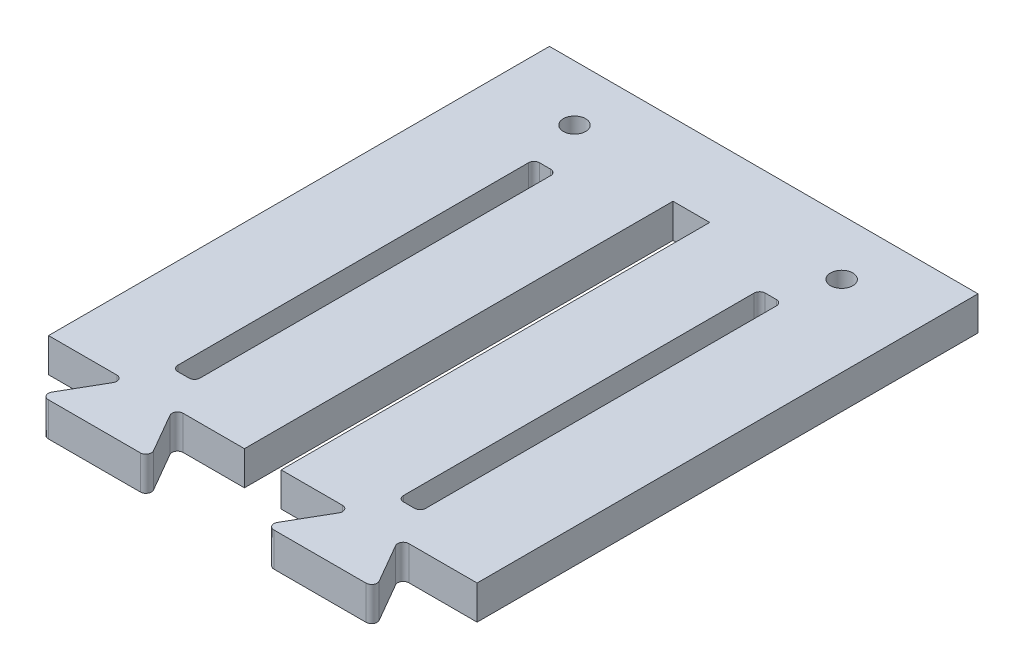
SolidWorks part; units mm, degrees
ref_plane "Front Plane" through (0, 0, 0) normal (0, 0, 1) x (1, 0, 0)
ref_plane "Top Plane" through (0, 0, 0) normal (0, 1, 0) x (1, 0, 0)
ref_plane "Right Plane" through (0, 0, 0) normal (1, 0, 0) x (0, 0, -1)
sketch "Sketch1" plane through (0, 0, 0) normal (0, 1, 0) x (1, 0, 0)
  line L0 (-19.25, 0) -> (-19.25, 45)
  line L1 (-19.25, 45) -> (19.25, 45)
  line L2 (19.25, 45) -> (19.25, 0)
  line L3 (19.25, 0) -> (12.25, 0)
  line L4 (12.25, 0) -> (15.1368, -5)
  line L5 (15.1368, -5) -> (5.1368, -5)
  line L6 (5.1368, -5) -> (8.0235, 0)
  line L7 (8.0235, 0) -> (-8.0235, 0)
  line L8 (-8.0235, 0) -> (-5.1368, -5)
  line L9 (-5.1368, -5) -> (-15.1368, -5)
  line L10 (-15.1368, -5) -> (-12.25, 0)
  line L11 (-12.25, 0) -> (-19.25, 0)
  point P13 (0, 0)
  dimension "D1" = 45
  dimension "D2" = 38.5
  dimension "D3" = 10
  dimension "D4" = 10
  dimension "D5" = 60
  dimension "D6" = 60
  dimension "D7" = 7
  dimension "D8" = 7
  dimension "D9" = 5
  dimension "D10" = 5
extrude "Boss-Extrude1" add sketch "Sketch1" along normal blind 3.05
fillet "Fillet1" radius 0.5 8 edges at (12.25, 1.525, 0) (15.1368, 1.525, 5) (5.1368, 1.525, 5) (8.0235, 1.525, 0) (-8.0235, 1.525, 0) (-5.1368, 1.525, 5) (-15.1368, 1.525, 5) (-12.25, 1.525, 0)
sketch "Sketch3" plane through (0, 3.05, 0) normal (0, 1, 0) x (1, 0, 0)
  line L0 (0, 40) -> (0, 0) construction
  line L2 (19.25, 45) -> (-19.25, 45) construction
  line L3 (-1.65, 38.5) -> (1.65, 38.5)
  line L4 (-1.65, 38.5) -> (-1.65, -1.5)
  line L5 (-1.65, -1.5) -> (1.65, -1.5)
  line L6 (1.65, 38.5) -> (1.65, -1.5)
  line L8 (-1.65, -2.7) -> (1.65, -2.7)
  line L9 (-1.65, -2.7) -> (-1.65, -3.7)
  line L10 (-1.65, -3.7) -> (1.65, -3.7)
  line L11 (1.65, -2.7) -> (1.65, -3.7)
  point P8 (0, 38.5)
  point P15 (0, -2.7)
  dimension "D1" = 3.3
  dimension "D2" = 40
  dimension "D3" = 6.5
  dimension "D4" = 1.2
  dimension "D5" = 1
extrude "Cut-Extrude2" cut sketch "Sketch3" against normal through all
sketch "Sketch8" plane through (0, 3.05, 0) normal (0, 1, 0) x (1, 0, 0)
  line L0 (0, 0) -> (0, 40) construction
  line L1 (-11.1368, 35.5) -> (-9.1368, 35.5)
  line L2 (-11.1368, 35.5) -> (-11.1368, 3)
  line L3 (-11.1368, 3) -> (-9.1368, 3)
  line L4 (-9.1368, 35.5) -> (-9.1368, 3)
  line L5 (-19.25, 0) -> (-13.116, 0) construction
  line L6 (-14.2707, -5) -> (-6.0028, -5) construction
  line L8 (11.1368, 3) -> (9.1368, 3)
  line L9 (9.1368, 35.5) -> (9.1368, 3)
  line L10 (11.1368, 35.5) -> (9.1368, 35.5)
  line L11 (11.1368, 35.5) -> (11.1368, 3)
  line L12 (1.65, 38.5) -> (-1.65, 38.5) construction
  point P5 (-10.1368, -5)
  point P10 (-10.1368, 3)
  dimension "D1" = 2
  dimension "D2" = 3
  dimension "D3" = 3
extrude "Cut-Extrude3" cut sketch "Sketch8" against normal through all
fillet "Fillet2" radius 0.5 8 edges at (11.1368, 1.525, -3) (9.1368, 1.525, -3) (11.1368, 1.525, -35.5) (9.1368, 1.525, -35.5) (-9.1368, 1.525, -3) (-9.1368, 1.525, -35.5) (-11.1368, 1.525, -35.5) (-11.1368, 1.525, -3)
sketch "Damper Hole Locations" plane through (0, 3.05, 0) normal (0, 1, 0) x (1, 0, 0)
  line L0 (0, 40) -> (0, 0) construction
  line L3 (19.25, 45) -> (-19.25, 45) construction
  circle A0 centre (-12, 40) radius 1.5
  circle A1 centre (12, 40) radius 1.5
  dimension "D1" = 3
  dimension "D2" = 12
  dimension "D3" = 5
hole_wizard "M3 Tapped Damper Holes" positions "Sketch6" profile "Sketch7" hole size "Ø2.0" standard "ANSI Metric" end condition through all
sketch "Sketch6" plane through (0, 3.05, 0) normal (0, 1, 0) x (1, 0, 0)
  point P0 (-12, 40)
  point P3 (12, 40)
sketch "Sketch7" plane through (-12, 3.05, -40) normal (1, 0, 0) x (0, 0, 1)
  line L0 (0, 0) -> (0, 3.05)
  line L1 (0, 3.05) -> (1, 3.05)
  line L2 (1, 3.05) -> (1, 0)
  line L5 (1, 0) -> (0, 0)
  line L11 (0, -6.35) -> (0, 107.95) construction
  dimension "Thru Hole Dia." = 2
  dimension "Thru Hole Depth" = 3.05
